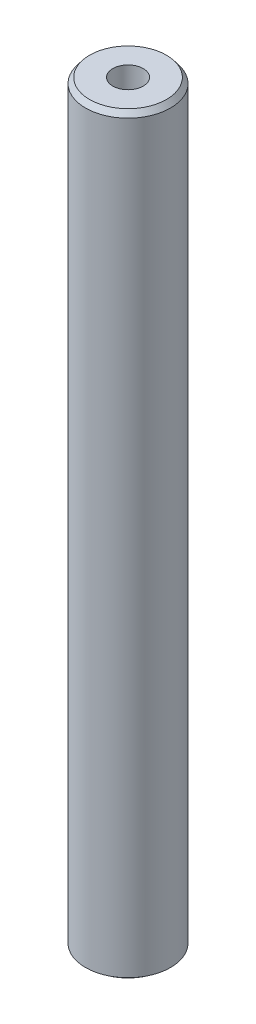
SolidWorks part; units mm, degrees
ref_plane "Front Plane" through (0, 0, 0) normal (0, 0, 1) x (1, 0, 0)
ref_plane "Top Plane" through (0, 0, 0) normal (0, 1, 0) x (1, 0, 0)
ref_plane "Right Plane" through (0, 0, 0) normal (1, 0, 0) x (0, 0, -1)
sketch "Sketch1" plane through (0, 0, 0) normal (0, 1, 0) x (1, 0, 0)
  circle A0 centre (0, 0) radius 17.5
  dimension "SHAFT_OD" = 35
extrude "Boss-Extrude1" add sketch "Sketch1" along normal blind 310.6493
sketch "Sketch2" plane through (0, 0, 0) normal (0, 1, 0) x (1, 0, 0)
  circle A0 centre (0, 0) radius 6.2748
  dimension "BORE_D" = 12.5497
extrude "Cut-Extrude1" cut sketch "Sketch2" along normal through all
chamfer "Chamfer1" distance 2.2139 angle 36.887 2 edges at (0, 310.6493, 17.5) (0, 0, 17.5) first distance on face at (0, 310.6493, 17.5) first distance on face at (0, 0, 6.2748)
